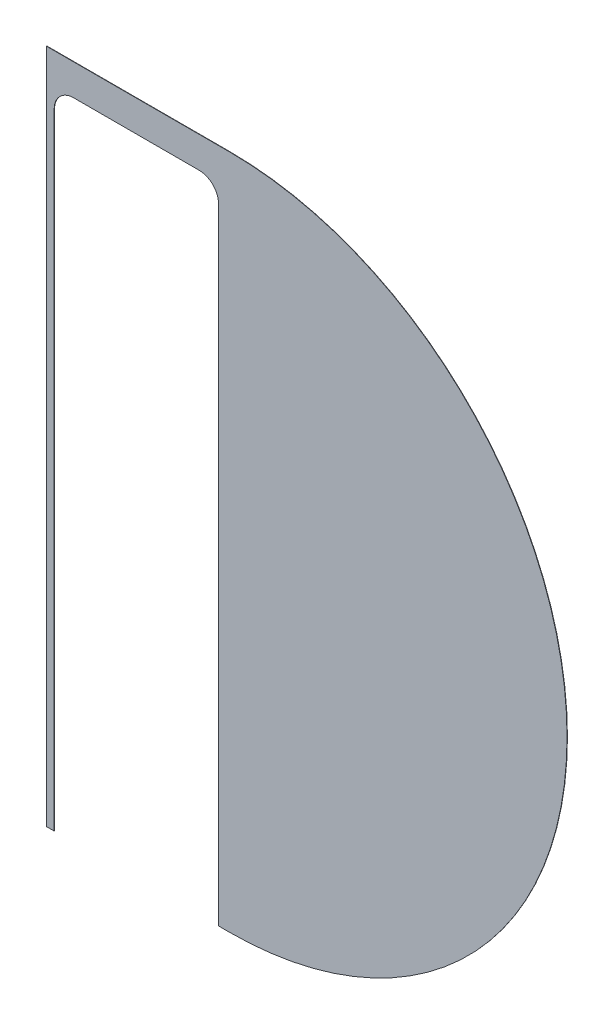
SolidWorks part; units mm, degrees
ref_plane "Front Plane" through (0, 0, 0) normal (0, 0, 1) x (1, 0, 0)
ref_plane "Top Plane" through (0, 0, 0) normal (0, 1, 0) x (1, 0, 0)
ref_plane "Right Plane" through (0, 0, 0) normal (1, 0, 0) x (0, 0, -1)
sketch "Sketch1" plane through (0, 0, 0) normal (0, 0, 1) x (1, 0, 0)
  line L1 (0, 0) -> (470, 0)
  line L2 (0, 0) -> (0, 1740)
  line L3 (0, 1740) -> (470, 1740)
  line L4 (470, 0) -> (470, 1740) construction
  arc A0 (470, 1740) -> (470, 0) centre (470, 870) cw
  dimension "D1" = 470
  dimension "D2" = 1740
extrude "Boss-Extrude1" add sketch "Sketch1" along normal blind 1
extrude "Cut-Extrude1" cut sketch "Sketch2" against normal through all
sketch "Sketch2" plane through (-149.8935, 64.2521, -32) normal (0, 0, -1) x (-1, 0, 0)
  line L1 (-592.7736, -114.2521) -> (-169.5721, -114.2521)
  line L2 (-592.7736, -114.2521) -> (-592.7736, 1545.5946)
  line L3 (-542.7736, 1595.5946) -> (-219.5721, 1595.5946)
  line L4 (-169.5721, -114.2521) -> (-169.5721, 1545.5946)
  arc A0 (-219.5721, 1595.5946) -> (-169.5721, 1545.5946) centre (-219.5721, 1545.5946) cw
  arc A1 (-592.7736, 1545.5946) -> (-542.7736, 1595.5946) centre (-542.7736, 1545.5946) cw
